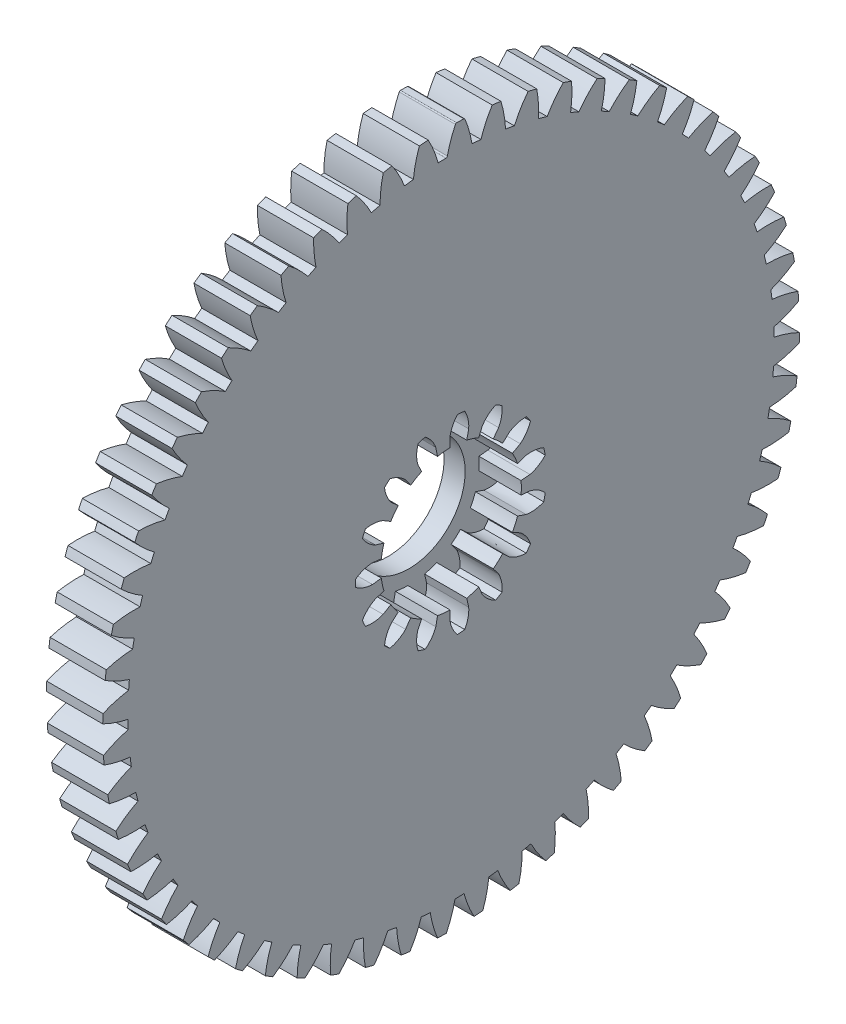
SolidWorks part; units mm, degrees
material "ABS"
ref_plane "Спереди" through (0, 0, 0) normal (0, 0, 1) x (1, 0, 0)
ref_plane "Сверху" through (0, 0, 0) normal (0, 1, 0) x (1, 0, 0)
ref_plane "Справа" through (0, 0, 0) normal (1, 0, 0) x (0, 0, -1)
sketch "Эскиз1" plane through (0, 0, 0) normal (1, 0, 0) x (0, 0, -1)
  circle A0 centre (0, 0) radius 23
  dimension "D1" = 46
extrude "Бобышка-Вытянуть1" add sketch "Эскиз1" along normal blind 4
sketch "Эскиз4" plane through (0, 0, 0) normal (-1, 0, 0) x (0, 0, 1)
  circle A0 centre (0, 0) radius 5
  dimension "D1" = 10
extrude "Бобышка-Вытянуть3" add sketch "Эскиз4" along normal blind 0.5
fillet "Скругление2" radius 0.5 1 edges at (0, 0, 5)
sketch "Эскиз5" plane through (-0.5, 0, 0) normal (-1, 0, 0) x (0, 0, 1)
  circle A0 centre (0, 0) radius 4
  dimension "D1" = 8
ref_plane "Плоскость1" through (2, 0, 0) normal (1, 0, 0) x (0, 0, -1)
sketch "Эскиз8" plane through (2, 0, 0) normal (1, 0, 0) x (0, 0, -1)
  line L0 (0, 0) -> (0, 24) construction
  line L1 (0, 24) -> (1.2462, 24) construction
  line L2 (0, 24) -> (7.7135, 21.1925) construction
  line L3 (0.335, 24.7977) -> (9.6573, 20.3803) construction
  line L4 (-0.2827, 22.9983) -> (4.1543, 22.1667) construction
  line L5 (0, 0) -> (0.6492, 24.7915) construction
  arc A0 (0.9633, 24.7813) -> (0.335, 24.7977) centre (0, 0) ccw
  circle A1 centre (0, 0) radius 24 construction
  circle A2 centre (0, 0) radius 22.5526 construction
  circle A3 centre (0, 0) radius 23 construction
  arc A5 (1.486, 22.9519) -> (-0.2827, 22.9983) centre (0, 0) ccw
  spline S0 degree 2 poles (-0.2827, 22.9983) (-0.084, 23.9365) (0.335, 24.7977) knots 0 0 0 1 1 1
  spline S1 degree 2 poles (1.486, 22.9519) (1.3366, 23.8993) (0.9633, 24.7813) knots 0 0 0 1 1 1
  dimension "D1" = 49.6
  dimension "D2" = 48
  dimension "D3" = 20
  dimension "D4" = 8.2085
  dimension "D5" = 10.316
  dimension "D7" = 4.5143
  dimension "D9" = 1.5
  dimension "D6" = 2.1075
  dimension "D8" = 3.6942
extrude "Бобышка-Вытянуть5" add sketch "Эскиз8" along normal up to surface and the other way up to surface up to face at (4, 0, -23) other way up to face at (0, 0, -5.5)
sketch "Эскиз10" plane through (4, 0, 0) normal (1, 0, 0) x (0, 0, -1)
  circle A0 centre (0, 0) radius 5
  dimension "D1" = 10
extrude "Вырез-Вытянуть2" cut sketch "Эскиз10" against normal blind 3
sketch "Эскиз9" plane through (4, 0, 0) normal (1, 0, 0) x (0, 0, -1)
  line L0 (0, 0) -> (0, 6) construction
  line L1 (0, 6) -> (1.2298, 6) construction
  line L2 (0, 6) -> (1.9284, 5.2981) construction
  line L3 (0.4492, 6.7851) -> (3.4539, 4.4564) construction
  line L4 (0, 0) -> (-0.084, 5.6375) construction
  line L5 (-0.084, 5.6375) -> (-0.0745, 4.9994)
  line L6 (0, 0) -> (0.7108, 6.7627) construction
  line L7 (1.2543, 5.4969) -> (1.1123, 4.8747)
  arc A0 (0.9713, 6.7303) -> (0.4492, 6.7851) centre (0, 0) ccw
  circle A1 centre (0, 0) radius 6 construction
  circle A2 centre (0, 0) radius 5 construction
  arc A3 (1.1123, 4.8747) -> (-0.0745, 4.9994) centre (0, 0) ccw
  circle A4 centre (0, 0) radius 5.6382 construction
  spline S0 degree 2 poles (-0.084, 5.6375) (0.0098, 6.2791) (0.4492, 6.7851) knots 0 0 0 1 1 1
  spline S1 degree 2 poles (1.2543, 5.4969) (1.296, 6.1439) (0.9713, 6.7303) knots 0 0 0 1 1 1
  point P11 (-0.084, 5.6375)
  dimension "D1" = 12
  dimension "D2" = 13.6
  dimension "D3" = 20
  dimension "D4" = 2.0521
  dimension "D5" = 3.8015
  dimension "D8" = 6
  dimension "D6" = 1.7494
  dimension "D7" = 2.0521
fillet "Скругление3" radius 0.1 4 edges at (2, 22.9983, 0.2827) (2, 22.9519, -1.486) (2, 24.7977, -0.335) (2, 24.7813, -0.9633)
extrude "Вырез-Вытянуть1" cut sketch "Эскиз5" against normal through all
extrude "Вырез-Вытянуть3" cut sketch "Эскиз9" against normal up to surface (3 mm away) up to face at (1, 0, -4)
pattern_circular "Круговой массив1" count 15 over 360 about axis through (1, 0, 0) along (1, 0, 0) of "Вырез-Вытянуть3" reverse direction yes
pattern_circular "Круговой массив2" count 60 over 360 about axis through (4, 0, 0) along (-1, 0, 0) of "Бобышка-Вытянуть5" reverse direction yes
equation "\"Модуль\"= 0.8мм"
equation "\"Число1\"= 60"
equation "\"Число2\"= 15"
equation "\"D1@Эскиз1\"= \"Модуль\" * (\"Число1\" - 2.5)"
equation "\"D1@Эскиз10\"= \"Модуль\" * ( \"Число2\" - 2.5 )"
equation "\"D1@Эскиз8\"= \"Модуль\" * (\"Число1\"  + 2)"
equation "\"D2@Эскиз8\"= \"Модуль\" * \"Число1\""
equation "\"D6@Эскиз8\"= \"D5@Эскиз8\" - \"D4@Эскиз8\""
equation "\"D8@Эскиз8\"= \"D4@Эскиз8\" - \"D7@Эскиз8\""
equation "\"D1@Круговой массив1\"=\"Число2\""
equation "\"D1@Эскиз9\"= \"Модуль\" * \"Число2\""
equation "\"D2@Эскиз9\"= \"Модуль\" * (\"Число2\" + 2)"
equation "\"D6@Эскиз9\"= \"D5@Эскиз9\" - \"D4@Эскиз9\""
equation "\"D7@Эскиз9\"= \"D4@Эскиз9\""
equation "\"D8@Эскиз9\"= 90 / \"Число2\""
equation "\"D1@Круговой массив2\"=\"Число1\""
